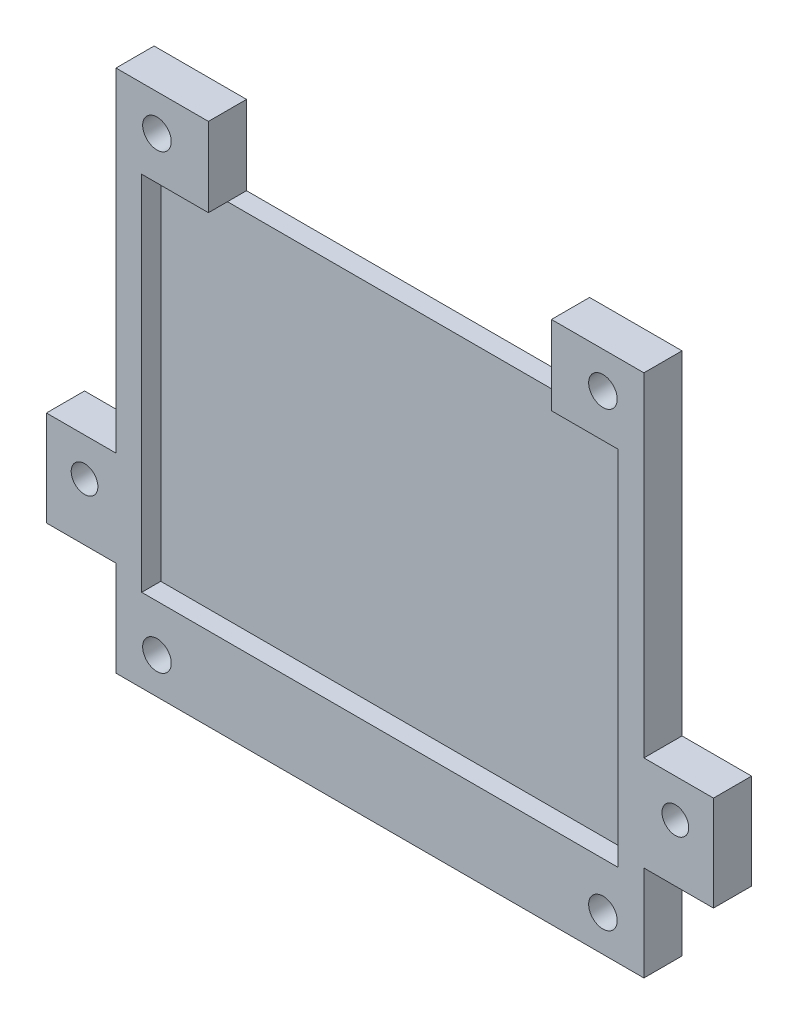
SolidWorks part; units mm, degrees
note: The reader was unsure of these and kept them because the rebuilt part matched: shared geometry of "草图2<3>".
ref_plane "前视基准面" through (0, 0, 0) normal (0, 0, 1) x (1, 0, 0)
ref_plane "上视基准面" through (0, 0, 0) normal (0, 1, 0) x (1, 0, 0)
ref_plane "右视基准面" through (0, 0, 0) normal (1, 0, 0) x (0, 0, -1)
other "Configuration Table"
sketch "草图1" plane through (0, 0, 0) normal (0, 0, 1) x (1, 0, 0)
  line L9 (-13.85, 13.75) -> (13.85, 13.75)
  line L10 (-13.85, 13.75) -> (-13.85, -13.75)
  line L11 (-13.85, -13.75) -> (13.85, -13.75)
  line L12 (13.85, 13.75) -> (13.85, -13.75)
  line L13 (-13.85, 13.75) -> (-15.85, 13.75)
  line L14 (-13.85, 13.75) -> (-13.85, -13.75)
  line L15 (-13.85, -13.75) -> (-15.85, -13.75)
  line L16 (-15.85, 13.75) -> (-15.85, -13.75)
  line L17 (13.85, -13.75) -> (15.85, -13.75)
  line L18 (13.85, -13.75) -> (13.85, 13.75)
  line L19 (13.85, 13.75) -> (15.85, 13.75)
  line L20 (15.85, -13.75) -> (15.85, 13.75)
  line L21 (-15.85, 13.75) -> (-18.85, 13.75)
  line L42 (-15.85, 13.75) -> (-15.85, 10.75)
  line L43 (-15.85, 10.75) -> (-18.85, 10.75)
  line L44 (-18.85, 13.75) -> (-18.85, 10.75)
  line L45 (-15.85, -13.75) -> (-18.85, -13.75)
  line L46 (-15.85, -13.75) -> (-15.85, -10.75)
  line L47 (-15.85, -10.75) -> (-18.85, -10.75)
  line L48 (-18.85, -13.75) -> (-18.85, -10.75)
  line L49 (15.85, -13.75) -> (18.85, -13.75)
  line L50 (15.85, -13.75) -> (15.85, -10.75)
  line L51 (15.85, -10.75) -> (18.85, -10.75)
  line L52 (18.85, -13.75) -> (18.85, -10.75)
  line L53 (15.85, 13.75) -> (18.85, 13.75)
  line L54 (15.85, 13.75) -> (15.85, 10.75)
  line L55 (15.85, 10.75) -> (18.85, 10.75)
  line L56 (18.85, 13.75) -> (18.85, 10.75)
  circle A12 centre (-17.35, 12.25) radius 0.6
  circle A13 centre (-17.35, -12.25) radius 0.6
  circle A14 centre (17.35, -12.25) radius 0.6
  circle A15 centre (17.35, 12.25) radius 0.6
  point P4 (0, 13.75)
  point P6 (-13.85, 0)
  point P32 (-17.35, 13.75)
  point P33 (-18.85, 12.25)
  point P35 (18.85, -12.25)
  point P37 (17.35, -13.75)
  dimension "D4" = 3
  dimension "D1" = 27.5
  dimension "D2" = 27.7
  dimension "D3" = 2
  dimension "D6" = 1.2
  dimension "D5" = 3
extrude "凸台-拉伸1" add sketch "草图1" along normal blind 2
sketch "草图2" plane through (0, 0, 2) normal (0, 0, 1) x (1, 0, 0)
  line L1 (-9, 9.6) -> (9, 9.6)
  line L2 (-9, 9.6) -> (-9, 13.75)
  line L3 (-9, 13.75) -> (9, 13.75)
  line L4 (9, 9.6) -> (9, 13.75)
  line L5 (-13.85, 13.75) -> (13.85, 13.75) construction
  line L7 (-12.5, 9.6) -> (12.5, 9.6)
  line L8 (-12.5, 9.6) -> (-12.5, -9.4)
  line L9 (-12.5, -9.4) -> (12.5, -9.4)
  line L10 (12.5, 9.6) -> (12.5, -9.4)
  circle A0 centre (-11.7, 11.85) radius 0.75
  circle A1 centre (11.7, 11.85) radius 0.75
  circle A2 centre (-11.7, -11.85) radius 0.75
  circle A3 centre (11.7, -11.85) radius 0.75
  point P4 (0, 13.75)
  point P30 (0, -9.4)
  dimension "D3" = 1.5
  dimension "D1" = 4.15
  dimension "D2" = 18
  dimension "D4" = 25
  dimension "D5" = 19
extrude "切除-拉伸1" cut sketch "草图2" against normal through all contours A0 | L2 L3 L4 L1 | A1 | A3 | A2
extrude "切除-拉伸2" cut sketch "草图2<3>" against normal blind 1 contours L9 L10 L7 L8
sketch "草图2<3>" plane through (0, 0, 2) normal (0, 0, 1) x (1, 0, 0) same geometry as "草图2"
sketch "草图3" plane through (0, 0, 1) normal (0, 0, 1) x (1, 0, 0)
  line L0 (-13.85, -13.75) -> (13.85, -13.75) construction
  line L1 (17.5, -8.75) -> (-17.5, -8.75)
  line L2 (17.5, -8.75) -> (17.5, -3.75)
  line L3 (17.5, -3.75) -> (-17.5, -3.75)
  line L4 (-17.5, -8.75) -> (-17.5, -3.75)
  line L5 (-17.5, -4.3965) -> (-13.85, -4.3965)
  line L7 (-13.85, 13.75) -> (-13.85, -13.75) construction
  line L9 (13.85, -4.3965) -> (17.5, -4.3965)
  line L10 (13.85, 13.75) -> (13.85, -13.75) construction
  circle A0 centre (-15.5, -5.75) radius 0.7
  circle A1 centre (15.5, -5.75) radius 0.7
  point P20 (0, 0)
  dimension "D7" = 1.4
  dimension "D1" = 5
  dimension "D2" = 5
  dimension "D3" = 35
  dimension "D4" = 2
  dimension "D5" = 2
  dimension "D6" = 2
extrude "凸台-拉伸2" add sketch "草图3" against normal up to surface (2 mm away) from surface
